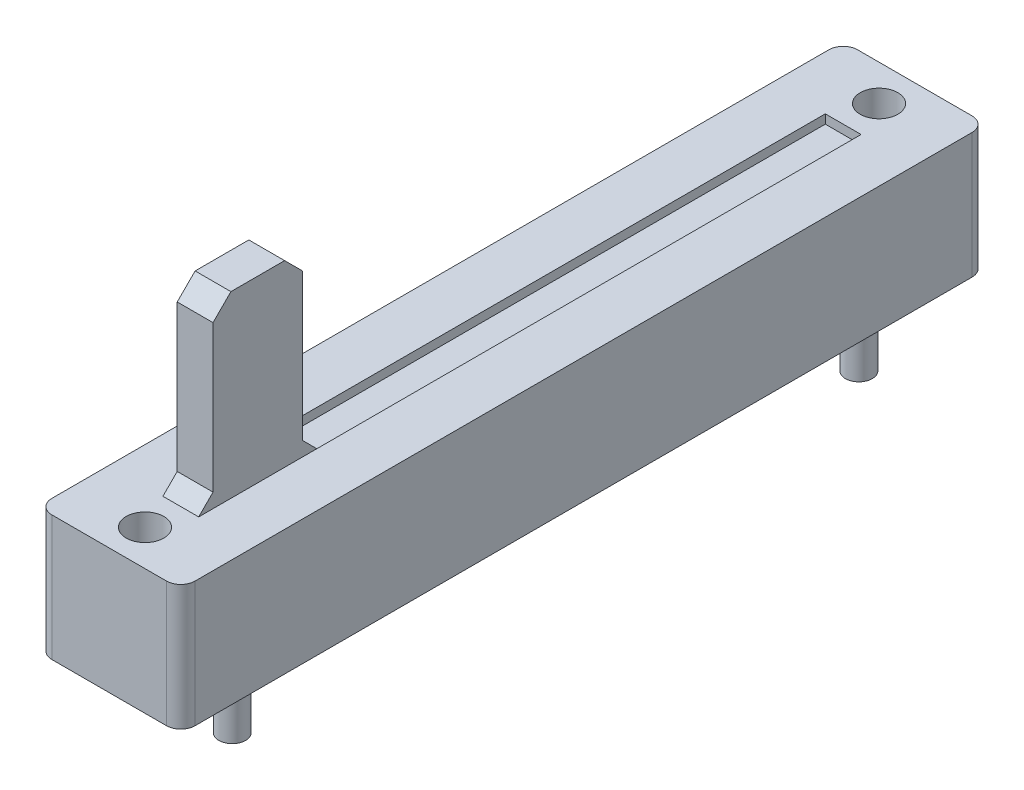
SolidWorks part; units mm, degrees
ref_plane "Płaszczyzna przednia" through (0, 0, 0) normal (0, 0, 1) x (1, 0, 0)
ref_plane "Płaszczyzna górna" through (0, 0, 0) normal (0, 1, 0) x (1, 0, 0)
ref_plane "Płaszczyzna prawa" through (0, 0, 0) normal (1, 0, 0) x (0, 0, -1)
sketch "Szkic1" plane through (0, 0, 0) normal (0, 1, 0) x (1, 0, 0)
  line L1 (0, 0) -> (8, 0)
  line L2 (0, 0) -> (0, 45)
  line L3 (0, 45) -> (8, 45)
  line L4 (8, 0) -> (8, 45)
  dimension "D1" = 45
  dimension "D2" = 8
extrude "Dodanie-wyciągnięcie1" add sketch "Szkic1" along normal blind 7
sketch "Szkic2" plane through (0, 7, 0) normal (0, 1, 0) x (1, 0, 0)
  line L0 (8, 45) -> (0, 45) construction
  line L2 (0, 0) -> (8, 0) construction
  circle A0 centre (4, 2) radius 1.05
  circle A1 centre (4, 43) radius 1.05
  dimension "D2" = 2.1
  dimension "D3" = 2.1
  dimension "D4" = 2
  dimension "D1" = 2
extrude "Wytnij-wyciągnięcie1" cut sketch "Szkic2" against normal blind 7
sketch "Szkic3" plane through (0, 7, 0) normal (0, 1, 0) x (1, 0, 0)
  line L1 (3, 4) -> (5, 4)
  line L2 (3, 4) -> (3, 41)
  line L3 (3, 41) -> (5, 41)
  line L4 (5, 4) -> (5, 41)
  line L5 (0, 0) -> (8, 0) construction
  line L6 (8, 0) -> (8, 45) construction
  point P6 (4, 0)
  point P7 (4, 4)
  point P8 (8, 22.5)
  point P11 (5, 22.5)
  dimension "D1" = 37
  dimension "D2" = 2
extrude "Wytnij-wyciągnięcie2" cut sketch "Szkic3" against normal blind 0.5
sketch "Szkic4" plane through (0, 6.5, 0) normal (0, 1, 0) x (1, 0, 0)
  line L0 (5, 4) -> (5, 41) construction
  line L1 (3, 4) -> (5, 4)
  line L2 (3, 4) -> (3, 10.6)
  line L3 (3, 10.6) -> (5, 10.6)
  line L4 (5, 4) -> (5, 10.6)
  dimension "D1" = 6.6
extrude "Dodanie-wyciągnięcie4" add sketch "Szkic4" along normal blind 1.5
sketch "Szkic12" plane through (0, 8, 0) normal (0, 1, 0) x (1, 0, 0)
  line L0 (3, 10.6) -> (3, 4) construction
  line L1 (3, 4.8) -> (5, 4.8)
  line L2 (3, 4.8) -> (3, 9.8)
  line L3 (3, 9.8) -> (5, 9.8)
  line L4 (5, 4.8) -> (5, 9.8)
  line L5 (5, 4) -> (5, 10.6) construction
  line L6 (5, 10.6) -> (3, 10.6) construction
  dimension "D1" = 0.8
  dimension "D2" = 5
extrude "Dodanie-wyciągnięcie6" add sketch "Szkic12" along normal blind 9
chamfer "Sfazowanie4" distance 1 angle 45 4 edges at (4, 17, -9.8) (4, 8, -10.6) (4, 8, -4) (4, 17, -4.8)
sketch "Szkic13" plane through (0, 0, 0) normal (0, -1, 0) x (1, 0, 0)
  line L0 (4, -45) -> (4, 0) construction
  line L1 (8, -45) -> (0, -45) construction
  line L2 (0, 0) -> (8, 0) construction
  line L3 (0, -22.5) -> (8, -22.5) construction
  line L4 (0, -45) -> (0, 0) construction
  line L5 (8, 0) -> (8, -45) construction
  circle A0 centre (2.125, -40) radius 0.75
  circle A1 centre (5.875, -40) radius 0.75
  circle A2 centre (5.875, -5) radius 0.75
  dimension "D1" = 1.5
  dimension "D2" = 17.5
  dimension "D5" = 1.875
  dimension "D3" = 17.5
  dimension "D4" = 3.75
extrude "Dodanie-wyciągnięcie7" add sketch "Szkic13" along normal blind 3.5
fillet "Zaokrąglenie1" radius 0.8 4 edges at (0, 3.5, 0) (8, 3.5, 0) (8, 3.5, -45) (0, 3.5, -45)
